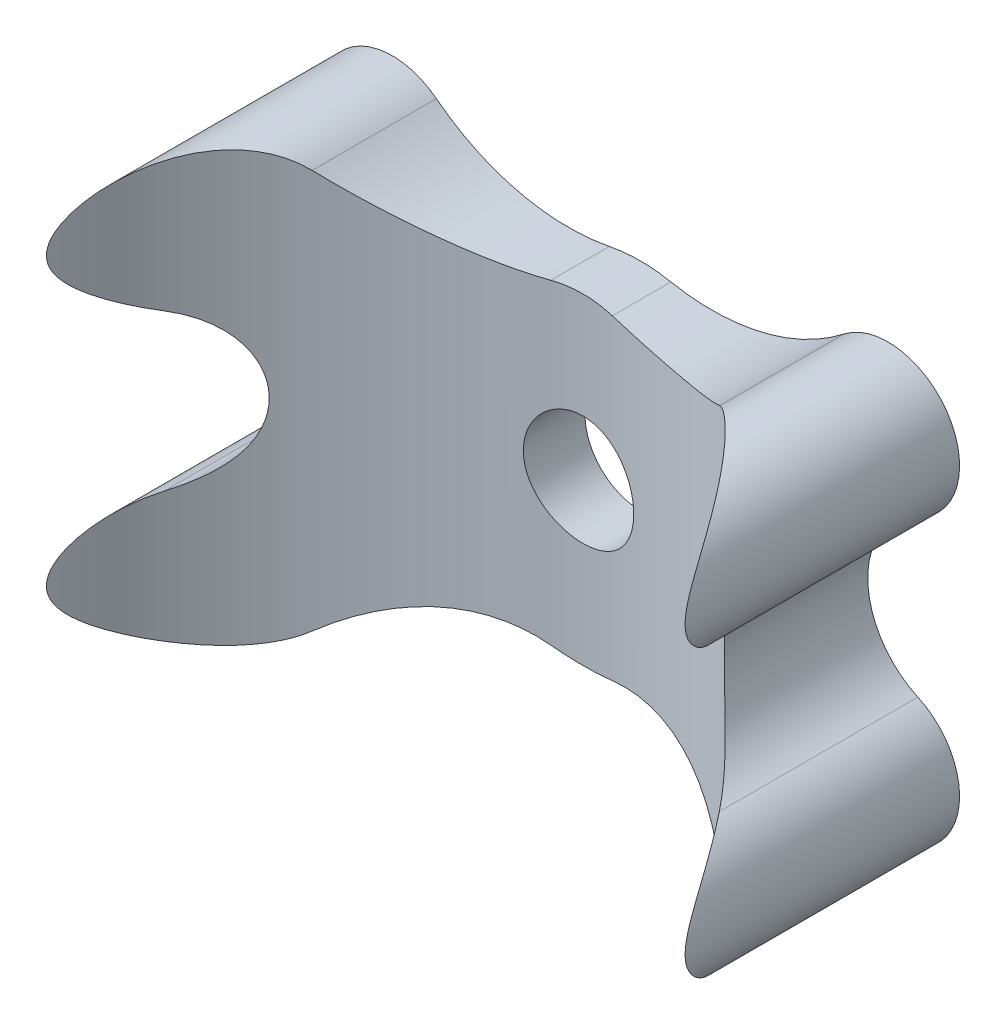
SolidWorks part; units mm, degrees
ref_plane "Front Plane" through (0, 0, 0) normal (0, 0, 1) x (1, 0, 0)
ref_plane "Top Plane" through (0, 0, 0) normal (0, 1, 0) x (1, 0, 0)
ref_plane "Right Plane" through (0, 0, 0) normal (1, 0, 0) x (0, 0, -1)
sketch "Sketch2" plane through (0, 0, 0) normal (1, 0, 0) x (0, 0, -1)
  line L5 (0, -76.2) -> (30.48, -76.2)
  line L6 (0, -76.2) -> (0, 76.2)
  line L7 (0, 76.2) -> (30.48, 76.2)
  line L8 (30.48, -76.2) -> (30.48, 76.2)
revolve "Revolve1" add sketch "Sketch2" angle 360 about L6
ref_plane "Plane1" through (0, 0, -30.48) normal (0, 0, -1) x (-1, 0, 0)
sketch "Sketch4" plane through (0, 0, -30.48) normal (0, 0, 1) x (-1, 0, 0)
  line L0 (0, 0) -> (-21.997, 12.7) construction
  line L1 (0, 0) -> (0, -14.2875) construction
  line L2 (0, 0) -> (21.997, 12.7) construction
  line L3 (-20.1969, 0) -> (20.1969, 0) construction
  arc A0 (-24.6424, -6.9273) -> (-24.6424, 6.9273) centre (-27.8169, 0) ccw
  arc A3 (24.6424, 6.9273) -> (18.0901, 17.7058) centre (21.997, 12.7) ccw
  arc A4 (2.7297, 14.0243) -> (18.0901, 17.7058) centre (6.3694, 32.7234) ccw
  arc A6 (24.6424, -6.9273) -> (18.0901, -17.7058) centre (21.997, -12.7) cw
  arc A7 (2.7297, -14.0243) -> (18.0901, -17.7058) centre (6.3694, -32.7234) cw
  arc A8 (24.6424, -6.9273) -> (24.6424, 6.9273) centre (27.8169, 0) cw
  circle A9 centre (0, 0) radius 4.8997
  arc A10 (-2.7297, -14.0243) -> (-18.0901, -17.7058) centre (-6.3694, -32.7234) ccw
  arc A11 (-24.6424, -6.9273) -> (-18.0901, -17.7058) centre (-21.997, -12.7) ccw
  arc A13 (-2.7297, 14.0243) -> (-18.0901, 17.7058) centre (-6.3694, 32.7234) cw
  arc A14 (-24.6424, 6.9273) -> (-18.0901, 17.7058) centre (-21.997, 12.7) cw
  arc A16 (2.7297, 14.0243) -> (-2.7297, 14.0243) centre (0, 0) ccw
  arc A17 (-2.7297, -14.0243) -> (2.7297, -14.0243) centre (0, 0) ccw
  circle A18 centre (21.997, 12.7) radius 2.54 construction
  circle A19 centre (21.997, -12.7) radius 2.54 construction
  circle A20 centre (-21.997, -12.7) radius 2.54 construction
  circle A21 centre (-21.997, 12.7) radius 2.54 construction
  point P6 (21.997, 10.16)
  point P35 (-21.997, 10.16)
  dimension "D1" = 5.08
  dimension "D4" = 12.7
  dimension "D5" = 5.08
  dimension "D6" = 7.62
  dimension "D2" = 19.05
  dimension "D3" = 30
  dimension "D7" = 10.16
extrude "Boss-Extrude1" add sketch "Sketch4" along normal blind 25.4 and the other way blind 5.08 separate body
sketch "Sketch8" plane through (0, 0, -35.56) normal (0, 0, -1) x (1, 0, 0)
  circle A2 centre (21.997, 12.7) radius 2.54
  circle A5 centre (21.997, -12.7) radius 2.54
  circle A12 centre (-21.997, -12.7) radius 2.54
  circle A15 centre (-21.997, 12.7) radius 2.54
  point P5 (21.997, 12.7)
  point P13 (21.997, -12.7)
  point P22 (-21.997, 12.7)
  point P29 (-21.997, -12.7)
  dimension "D1" = 5.08
hole_wizard "#8 (0.199) Diameter Hole1" positions "Sketch8" profile "Sketch10" hole size "#8" standard "ANSI Inch"
sketch "Sketch10" plane through (-21.997, 12.7, -35.56) normal (1, 0, 0) x (0, 1, 0)
  line L0 (0, 0) -> (0, 6.5986)
  line L1 (0, 6.5986) -> (2.5273, 5.08)
  line L2 (2.5273, 5.08) -> (2.5273, 0)
  line L5 (2.5273, 0) -> (0, 0)
  line L10 (0, 6.5986) -> (-2.5273, 5.08) construction
  line L11 (0, -6.35) -> (0, 107.95) construction
  dimension "Hole Dia." = 5.0546
  dimension "Hole Depth" = 5.08
  dimension "Drill Angle" = 118
combine bodies "Combine4" operation type subtract main body 107 bodies to subtract 101
